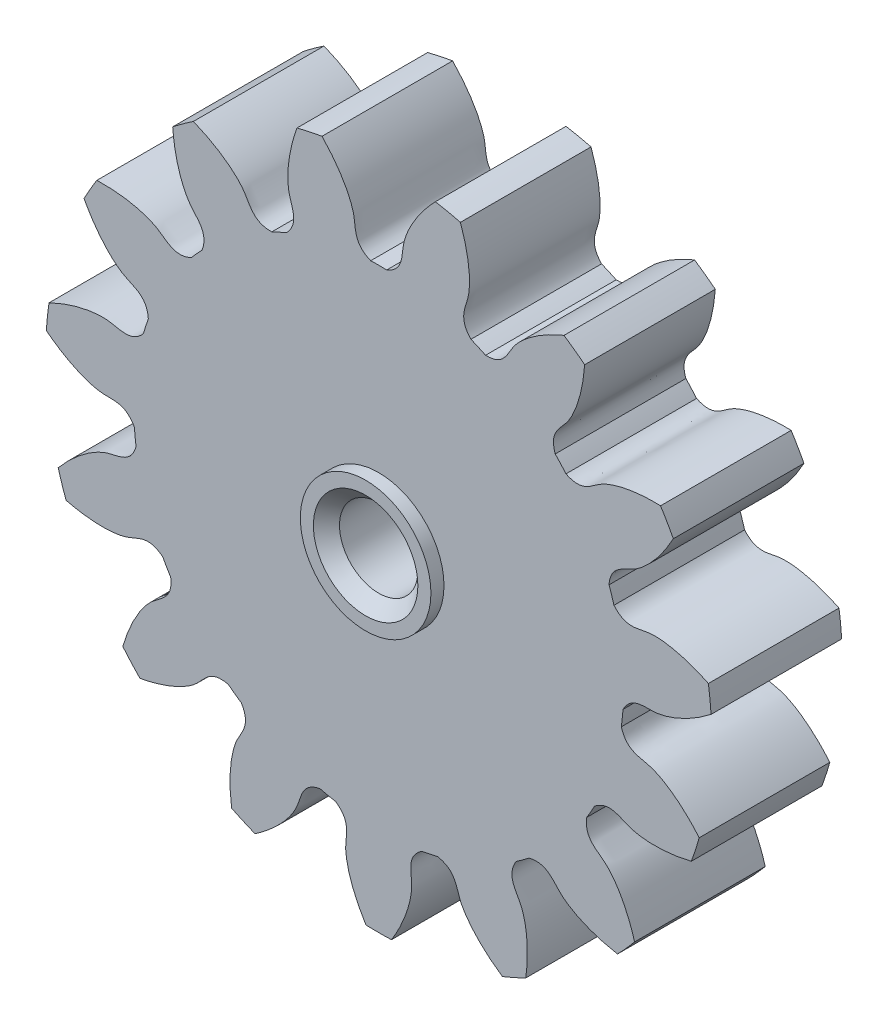
SolidWorks part; units mm, degrees
ref_plane "前视基准面" through (0, 0, 0) normal (0, 0, 1) x (1, 0, 0)
ref_plane "上视基准面" through (0, 0, 0) normal (0, 1, 0) x (1, 0, 0)
ref_plane "右视基准面" through (0, 0, 0) normal (1, 0, 0) x (0, 0, -1)
sketch "草图1" plane through (0, 0, 0) normal (0, 0, 1) x (1, 0, 0)
  circle A0 centre (0, 0) radius 12.75
extrude "凸台-拉伸1" add sketch "草图1" along normal blind 5
ref_axis "基准轴1" through (0, 0, -0.25) along (0, 0, 1)
sketch "草图2" plane through (0, 0, 0) normal (0, 0, 1) x (1, 0, 0)
  line L0 (0, 0) -> (0, 12.75) construction
  circle A0 centre (0, 0) radius 12.75 construction
  arc A1 (0.3064, 9.37) -> (-0.3064, 9.37) centre (0, 0) ccw
  arc A2 (4.8703, 14.4539) -> (-4.8703, 14.4539) centre (0, 0) ccw
  spline S0 degree 3 poles (0.3064, 9.37) (0.9858, 9.6516) (0.8582, 10.1795) (0.9769, 10.6628) (0.9861, 10.6975) (0.9973, 10.7361) (1.0104, 10.7785) (1.0257, 10.8247) (1.0434, 10.8745) (1.0635, 10.9279) (1.0863, 10.9848) (1.1118, 11.0452) (1.1403, 11.1089) (1.1718, 11.1759) (1.2066, 11.2459) (1.2447, 11.3191) (1.2863, 11.3952) (1.3315, 11.474) (1.3804, 11.5556) (1.4332, 11.6398) (1.49, 11.7265) (1.5509, 11.8155) (1.616, 11.9067) (1.6855, 11.9999) (1.7594, 12.0951) (1.8379, 12.1921) (1.921, 12.2907) (2.0088, 12.3909) (2.1015, 12.4924) (2.1991, 12.595) (2.3018, 12.6987) (2.4095, 12.8033) (2.5223, 12.9086) (2.6404, 13.0144) (2.7638, 13.1206) (2.8926, 13.227) (3.0268, 13.3335) (3.1664, 13.4398) (3.3116, 13.5458) (3.4623, 13.6512) (3.6186, 13.7561) (3.7805, 13.86) (3.948, 13.9629) (4.1213, 14.0646) (4.3002, 14.1648) (4.5489, 14.2977) (4.7402, 14.3926) (4.8703, 14.4539) knots 0 0 0 0 0.202473 0.206979 0.212085 0.217793 0.224101 0.23101 0.23852 0.24663 0.255341 0.264653 0.274566 0.285079 0.296194 0.307909 0.320225 0.333141 0.346659 0.360777 0.375496 0.390816 0.406736 0.423257 0.440379 0.458102 0.476426 0.49535 0.514875 0.535001 0.555728 0.577055 0.598984 0.621513 0.644642 0.668373 0.692704 0.717636 0.743169 0.769303 0.796037 0.823373 0.851309 0.879845 0.908983 0.938721 1 1 1 1
  spline S1 degree 3 poles (-0.3064, 9.37) (-0.9858, 9.6516) (-0.8582, 10.1795) (-0.9769, 10.6628) (-0.9861, 10.6975) (-0.9973, 10.7361) (-1.0104, 10.7785) (-1.0257, 10.8247) (-1.0434, 10.8745) (-1.0635, 10.9279) (-1.0863, 10.9848) (-1.1118, 11.0452) (-1.1403, 11.1089) (-1.1718, 11.1759) (-1.2066, 11.2459) (-1.2447, 11.3191) (-1.2863, 11.3952) (-1.3315, 11.474) (-1.3804, 11.5556) (-1.4332, 11.6398) (-1.49, 11.7265) (-1.5509, 11.8155) (-1.616, 11.9067) (-1.6855, 11.9999) (-1.7594, 12.0951) (-1.8379, 12.1921) (-1.921, 12.2907) (-2.0088, 12.3909) (-2.1015, 12.4924) (-2.1991, 12.595) (-2.3018, 12.6987) (-2.4095, 12.8033) (-2.5223, 12.9086) (-2.6404, 13.0144) (-2.7638, 13.1206) (-2.8926, 13.227) (-3.0268, 13.3335) (-3.1664, 13.4398) (-3.3116, 13.5458) (-3.4623, 13.6512) (-3.6186, 13.7561) (-3.7805, 13.86) (-3.948, 13.9629) (-4.1213, 14.0646) (-4.3002, 14.1648) (-4.5489, 14.2977) (-4.7402, 14.3926) (-4.8703, 14.4539) knots 0 0 0 0 0.202473 0.206979 0.212085 0.217793 0.224101 0.23101 0.23852 0.24663 0.255341 0.264653 0.274566 0.285079 0.296194 0.307909 0.320225 0.333141 0.346659 0.360777 0.375496 0.390816 0.406736 0.423257 0.440379 0.458102 0.476426 0.49535 0.514875 0.535001 0.555728 0.577055 0.598984 0.621513 0.644642 0.668373 0.692704 0.717636 0.743169 0.769303 0.796037 0.823373 0.851309 0.879845 0.908983 0.938721 1 1 1 1
extrude "切除-拉伸1" cut sketch "草图2" along normal through all
pattern_circular "阵列(圆周)1" count 15 every 24 about axis through (0, 0, -0.25) along (0, 0, 1) of "切除-拉伸1"
sketch "草图3" plane through (0, 0, 0) normal (0, 0, 1) x (1, 0, 0)
  circle A0 centre (0, 0) radius 11.25 construction
  dimension "Dn" = 22.5
sketch "草图4" plane through (0, 0, 5) normal (0, 0, 1) x (1, 0, 0)
  circle A0 centre (0, 0) radius 1.5
  dimension "D1" = 3
extrude "切除-拉伸2" cut sketch "草图4" against normal through all
sketch "草图5" plane through (0, 0, 5) normal (0, 0, 1) x (1, 0, 0)
  circle A0 centre (0, 0) radius 1.5 construction
  circle A1 centre (0, 0) radius 1.5
  circle A2 centre (0, 0) radius 2.5
  dimension "D1" = 5
extrude "凸台-拉伸2" add sketch "草图5" along normal blind 0.5
chamfer "倒角1" distance 0.5 angle 45 2 edges at (1.5, 0, 0) (1.5, 0, 5.5)
